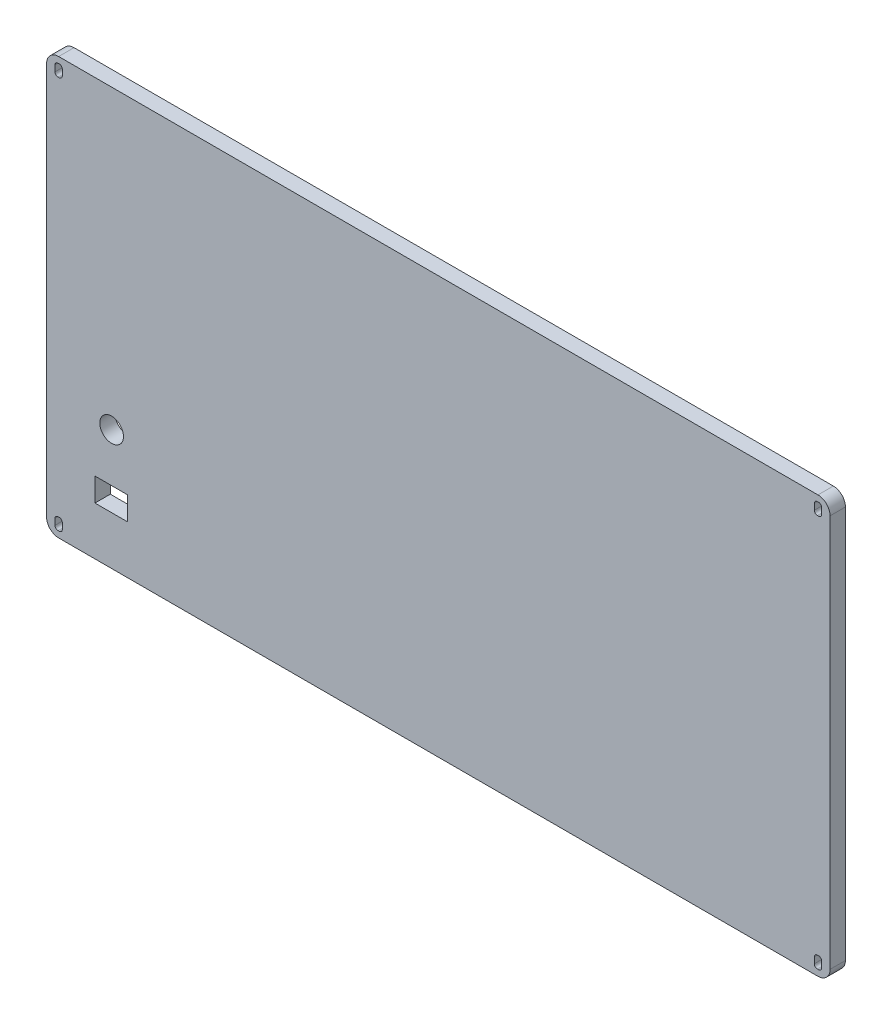
SolidWorks part; units mm, degrees
ref_plane "Front Plane" through (0, 0, 0) normal (0, 0, 1) x (1, 0, 0)
ref_plane "Top Plane" through (0, 0, 0) normal (0, 1, 0) x (1, 0, 0)
ref_plane "Right Plane" through (0, 0, 0) normal (1, 0, 0) x (0, 0, -1)
sketch "Sketch1" plane through (0, 0, 0) normal (0, 0, 1) x (1, 0, 0)
  line L0 (339.8604, -207.3242) -> (338.8604, -207.3242)
  line L1 (-298.3396, 132.3538) -> (349.3604, 132.3538)
  line L2 (-298.3396, 132.3538) -> (-298.3396, -212.3242)
  line L3 (-298.3396, -212.3242) -> (349.3604, -212.3242)
  line L4 (349.3604, 132.3538) -> (349.3604, -212.3242)
  line L5 (342.3604, -204.8242) -> (342.3604, -199.8242)
  line L6 (339.8604, -197.3242) -> (338.8604, -197.3242)
  line L7 (336.3604, -204.8242) -> (336.3604, -199.8242)
  line L8 (339.3604, -197.3242) -> (339.3604, -207.3242) construction
  line L9 (336.3604, -202.3242) -> (342.3604, -202.3242) construction
  line L10 (-287.8396, -207.3242) -> (-288.8396, -207.3242)
  line L11 (-291.3396, -204.8242) -> (-291.3396, -199.8242)
  line L12 (-287.8396, -197.3242) -> (-288.8396, -197.3242)
  line L13 (-285.3396, -204.8242) -> (-285.3396, -199.8242)
  line L14 (-287.8396, 117.3558) -> (-288.8396, 117.3558)
  line L15 (-291.3396, 119.8558) -> (-291.3396, 124.8558)
  line L16 (-287.8396, 127.3558) -> (-288.8396, 127.3558)
  line L17 (-285.3396, 119.8558) -> (-285.3396, 124.8558)
  line L18 (339.8604, 117.3558) -> (338.8604, 117.3558)
  line L19 (336.3604, 119.8558) -> (336.3604, 124.8558)
  line L20 (339.8604, 127.3558) -> (338.8604, 127.3558)
  line L21 (342.3604, 119.8558) -> (342.3604, 124.8558)
  line L23 (-258.3396, -152.9694) -> (-231.2378, -152.9694)
  line L24 (-258.3396, -152.9694) -> (-258.3396, -172.3242)
  line L25 (-258.3396, -172.3242) -> (-231.2378, -172.3242)
  line L26 (-231.2378, -152.9694) -> (-231.2378, -172.3242)
  arc A0 (339.8604, -207.3242) -> (342.3604, -204.8242) centre (339.8604, -204.8242) ccw
  arc A1 (342.3604, -199.8242) -> (339.8604, -197.3242) centre (339.8604, -199.8242) ccw
  arc A2 (338.8604, -207.3242) -> (336.3604, -204.8242) centre (338.8604, -204.8242) cw
  arc A3 (338.8604, -197.3242) -> (336.3604, -199.8242) centre (338.8604, -199.8242) ccw
  arc A4 (-288.8396, -207.3242) -> (-291.3396, -204.8242) centre (-288.8396, -204.8242) cw
  arc A5 (-288.8396, -197.3242) -> (-291.3396, -199.8242) centre (-288.8396, -199.8242) ccw
  arc A6 (-285.3396, -199.8242) -> (-287.8396, -197.3242) centre (-287.8396, -199.8242) ccw
  arc A7 (-287.8396, -207.3242) -> (-285.3396, -204.8242) centre (-287.8396, -204.8242) ccw
  arc A8 (-288.8396, 117.3558) -> (-291.3396, 119.8558) centre (-288.8396, 119.8558) cw
  arc A9 (-288.8396, 127.3558) -> (-291.3396, 124.8558) centre (-288.8396, 124.8558) ccw
  arc A10 (-285.3396, 124.8558) -> (-287.8396, 127.3558) centre (-287.8396, 124.8558) ccw
  arc A11 (-287.8396, 117.3558) -> (-285.3396, 119.8558) centre (-287.8396, 119.8558) ccw
  arc A12 (338.8604, 117.3558) -> (336.3604, 119.8558) centre (338.8604, 119.8558) cw
  arc A13 (338.8604, 127.3558) -> (336.3604, 124.8558) centre (338.8604, 124.8558) ccw
  arc A14 (342.3604, 124.8558) -> (339.8604, 127.3558) centre (339.8604, 124.8558) ccw
  arc A15 (339.8604, 117.3558) -> (342.3604, 119.8558) centre (339.8604, 119.8558) ccw
  circle A16 centre (-244.56, -112.9694) radius 9.779
  point P63 (0, 0)
  point P64 (0, 0)
  dimension "D6" = 2.5
  dimension "D17" = 40
  dimension "0.77" = 19.558
  dimension "D18" = 53.7797
  dimension "D1" = 647.7
  dimension "D2" = 132.3538
  dimension "12in" = 344.678
  dimension "D3" = 298.3396
  dimension "D4" = 6
  dimension "D5" = 10
  dimension "D7" = 10
  dimension "D8" = 10
  dimension "D11" = 7
  dimension "D12" = 4.998
  dimension "D13" = 7
  dimension "D14" = 27.1018
  dimension "D15" = 40
  dimension "0" = 19.3548
  dimension "D16" = 40
  dimension "D9" = 2
  dimension "D10" = 2
extrude "Boss-Extrude1" add sketch "Sketch1" along normal blind 12.7
fillet "Fillet1" radius 10 3 edges at (349.3604, -212.3242, 6.35) (349.3604, 132.3538, 6.35) (-298.3396, 132.3538, 6.35)
fillet "Fillet2" radius 10 1 edges at (-298.3396, -212.3242, 6.35)
